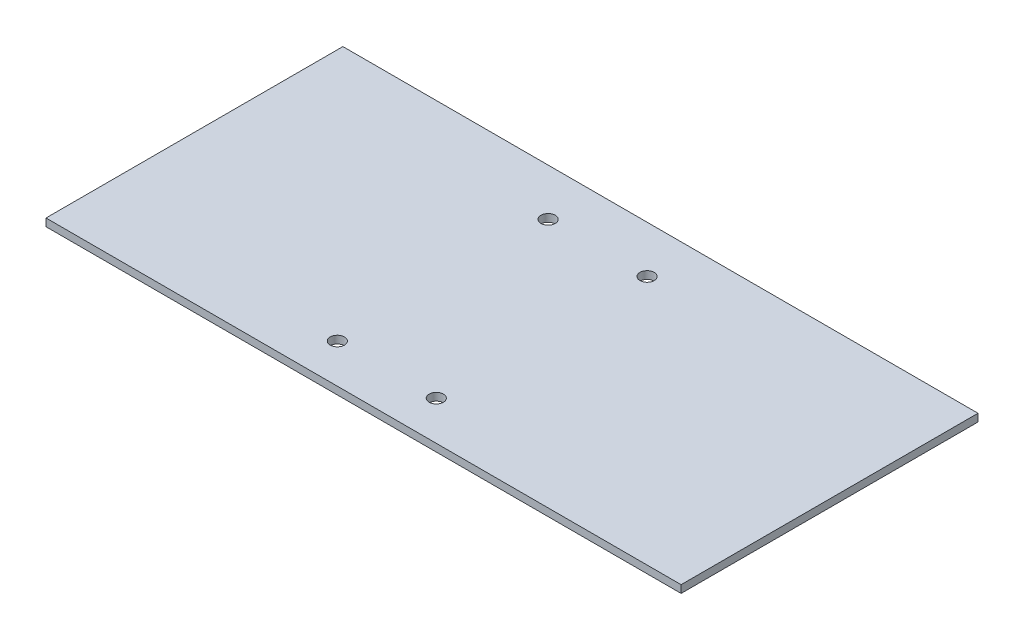
SolidWorks part; units mm, degrees
material "Thornel Mat VMA"
ref_plane "Front Plane" through (0, 0, 0) normal (0, 0, 1) x (1, 0, 0)
ref_plane "Top Plane" through (0, 0, 0) normal (0, 1, 0) x (1, 0, 0)
ref_plane "Right Plane" through (0, 0, 0) normal (1, 0, 0) x (0, 0, -1)
sketch "Sketch1" plane through (0, 0, 0) normal (0, 1, 0) x (1, 0, 0)
  line L1 (0, 0) -> (101.88, 0)
  line L2 (0, 0) -> (0, -47.625)
  line L3 (0, -47.625) -> (101.88, -47.625)
  line L4 (101.88, 0) -> (101.88, -47.625)
  dimension "D1" = 47.625
  dimension "D2" = 101.88
extrude "Boss-Extrude1" add sketch "Sketch1" along normal blind 1.2192
sketch "Sketch5" plane through (0, 1.2192, 0) normal (0, 1, 0) x (1, 0, 0)
  line L0 (101.88, 0) -> (0, 0) construction
  line L1 (56.3375, -7.5406) -> (40.4625, -7.5406) construction
  line L2 (0, 0) -> (0, -47.625) construction
  line L3 (101.88, -23.8125) -> (0, -23.8125) construction
  line L4 (101.88, -47.625) -> (101.88, 0) construction
  circle A0 centre (56.3375, -7.5406) radius 1.143
  circle A1 centre (40.4625, -7.5406) radius 1.143
  dimension "D1" = 2.286
  dimension "D2" = 2.286
  dimension "D3" = 15.875
  dimension "D4" = 7.5406
  dimension "D5" = 40.4625
extrude "Cut-Extrude1" cut sketch "Sketch5" against normal up to next
sketch "Sketch6" plane through (0, 1.2192, 0) normal (0, 1, 0) x (1, 0, 0)
  line L0 (56.3375, -41.3544) -> (40.4625, -41.3544) construction
  line L1 (0, 0) -> (0, -47.625) construction
  line L2 (0, -47.625) -> (101.88, -47.625) construction
  circle A0 centre (56.3375, -41.3544) radius 1.143
  circle A1 centre (40.4625, -41.3544) radius 1.143
  dimension "D1" = 2.286
  dimension "D2" = 2.286
  dimension "D3" = 15.875
  dimension "D4" = 6.2706
  dimension "D5" = 40.4625
extrude "Cut-Extrude2" cut sketch "Sketch6" against normal up to next
